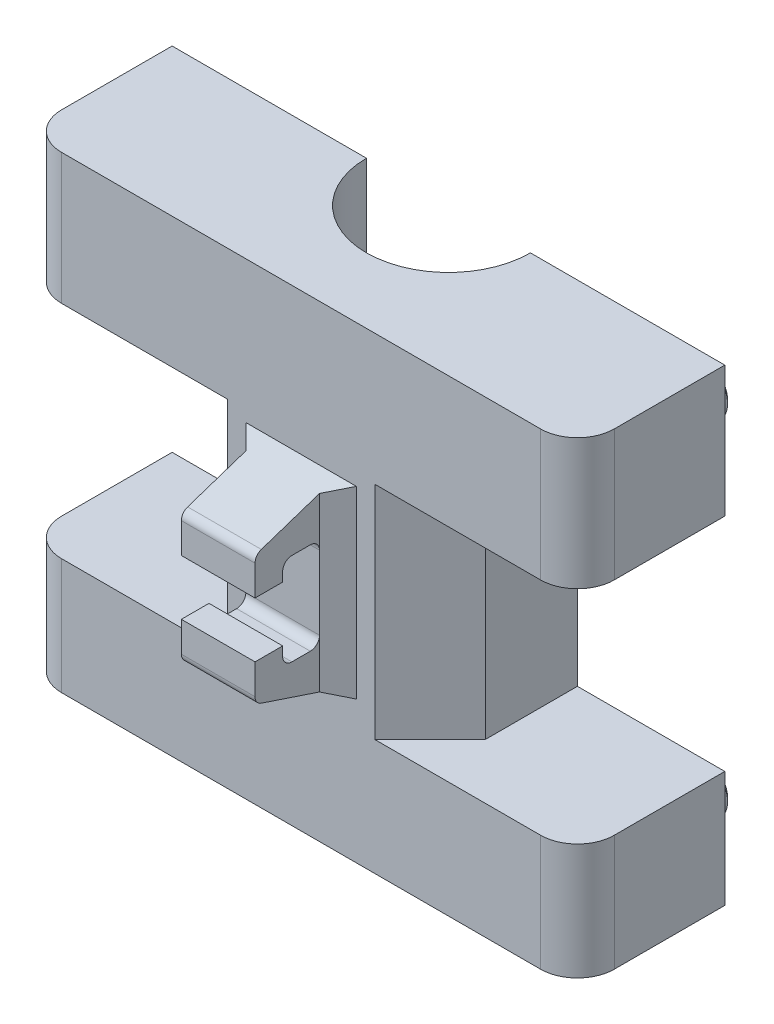
SolidWorks part; units mm, degrees
ref_plane "Front Plane" through (0, 0, 0) normal (0, 0, 1) x (1, 0, 0)
ref_plane "Top Plane" through (0, 0, 0) normal (0, 1, 0) x (1, 0, 0)
ref_plane "Right Plane" through (0, 0, 0) normal (1, 0, 0) x (0, 0, -1)
sketch "Sketch1" plane through (0, 0, 0) normal (0, 0, 1) x (1, 0, 0)
  line L1 (-15, 12.7) -> (15, 12.7)
  line L2 (-15, 12.7) -> (-15, -12.7)
  line L3 (-15, -12.7) -> (15, -12.7)
  line L4 (15, 12.7) -> (15, -12.7)
  line L5 (-15, 12.7) -> (15, -12.7) construction
  line L6 (-15, -12.7) -> (15, 12.7) construction
  point P0 (0, 0)
  dimension "D1" = 25.4
  dimension "D2" = 30
extrude "Boss-Extrude1" add sketch "Sketch1" along normal blind 8
sketch "Sketch2" plane through (0, 0, 0) normal (0, 1, 0) x (1, 0, 0)
  line L0 (15, 0) -> (-15, 0) construction
  circle A0 centre (0, 0) radius 4.45
  dimension "D1" = 8.9
extrude "Cut-Extrude1" cut sketch "Sketch2" against normal through all both and the other way through all
sketch "Sketch3" plane through (0, 0, 0) normal (0, 0, 1) x (1, 0, 0)
  line L0 (-15, 12.7) -> (-15, -12.7) construction
  line L1 (-12, 9.15) -> (12, 9.15) construction
  line L2 (-12, 9.15) -> (-12, -9.55) construction
  line L3 (-12, -9.55) -> (12, -9.55) construction
  line L4 (12, 9.15) -> (12, -9.55) construction
  line L5 (0, -9.55) -> (0, 9.15) construction
  line L6 (-12, -0.2) -> (12, -0.2) construction
  line L7 (15, -12.7) -> (15, 12.7) construction
  line L8 (15, 12.7) -> (-15, 12.7) construction
  line L9 (-15, -12.7) -> (15, -12.7) construction
  circle A0 centre (-12, 9.15) radius 1.35
  circle A1 centre (12, 9.15) radius 1.35
  circle A2 centre (12, -9.55) radius 1.35
  circle A3 centre (-12, -9.55) radius 1.35
  point P176 (0, -0.2)
  dimension "D4" = 2.7
  dimension "D1" = 3.55
  dimension "D2" = 24
  dimension "D3" = 3.15
extrude "Boss-Extrude2" add sketch "Sketch3" against normal blind 2
fillet "Fillet1" radius 0.3 4 edges at (-10.65, -9.55, 0) (13.35, -9.55, 0) (13.35, 9.15, 0) (-10.65, 9.15, 0)
chamfer "Chamfer1" distance 0.2 angle 45 4 edges at (13.35, 9.15, -2) (13.35, -9.55, -2) (-10.65, -9.55, -2) (-10.65, 9.15, -2)
sketch "Sketch4" plane through (0, 0, 0) normal (0, 0, 1) x (1, 0, 0)
  line L0 (-15, 12.7) -> (-15, -12.7) construction
  line L1 (-15, 5.6) -> (-7, 5.6)
  line L2 (-15, 5.6) -> (-15, -6.4)
  line L3 (-15, -6.4) -> (-7, -6.4)
  line L4 (-7, 5.6) -> (-7, -6.4)
  line L5 (-11, -6.4) -> (-11, 5.6) construction
  line L6 (-15, -0.4) -> (-7, -0.4) construction
  line L7 (15, -12.7) -> (15, 12.7) construction
  line L8 (15, 5.6) -> (7, 5.6)
  line L9 (15, 5.6) -> (15, -6.4)
  line L10 (15, -6.4) -> (7, -6.4)
  line L11 (7, 5.6) -> (7, -6.4)
  line L12 (11, -6.4) -> (11, 5.6) construction
  line L13 (15, -0.4) -> (7, -0.4) construction
  line L14 (-15, -12.7) -> (15, -12.7) construction
  line L15 (15, 12.7) -> (-15, 12.7) construction
  point P100 (-11, -0.4)
  point P323 (11, -0.4)
  dimension "D1" = 6.3
  dimension "D2" = 7.1
  dimension "D3" = 8
extrude "Cut-Extrude2" cut sketch "Sketch4" along normal through all
sketch "Sketch5" plane through (0, 0, 0) normal (1, 0, 0) x (0, 0, -1)
  line L0 (-8, 5) -> (-8, -5)
  line L1 (-8, 5.6) -> (-8, -6.4) construction
  line L2 (-8, -5) -> (-12.5, -3.5)
  line L3 (-12.5, -3.5) -> (-12.5, -1.5)
  line L4 (-12.5, -1.5) -> (-11, -1.5)
  line L5 (-11, -1.5) -> (-11, -2.5)
  line L6 (-11, -2.5) -> (-9, -2.5)
  line L7 (-9, -2.5) -> (-9, 2.5)
  line L8 (-9, 2.5) -> (-11, 2.5)
  line L9 (-11, 2.5) -> (-11, 1.5)
  line L10 (-11, 1.5) -> (-12.5, 1.5)
  line L11 (-12.5, 1.5) -> (-12.5, 3.5)
  line L12 (-12.5, 3.5) -> (-8, 5)
  point P4 (-8, 0)
  point P15 (-9, 0)
  dimension "D1" = 1
  dimension "D2" = 2
  dimension "D3" = 1.5
  dimension "D4" = 10
  dimension "D5" = 7
  dimension "D6" = 3
  dimension "D7" = 5
extrude "Boss-Extrude3" add sketch "Sketch5" along normal mid plane 4
chamfer "Chamfer2" distance 1 angle 45 2 edges at (2, 0, 8) (-2, 0, 8)
fillet "Fillet2" radius 0.5 6 edges at (0, -2.5, 11) (0, 2.5, 11) (0, -3.5, 12.5) (0, 3.5, 12.5) (0, -2.5, 9) (0, 2.5, 9)
chamfer "Chamfer3" distance 3 angle 45 2 edges at (7, -0.4, 8) (-7, -0.4, 8)
fillet "Fillet3" radius 2 4 edges at (-15, -9.55, 8) (15, -9.55, 8) (15, 9.15, 8) (-15, 9.15, 8)
